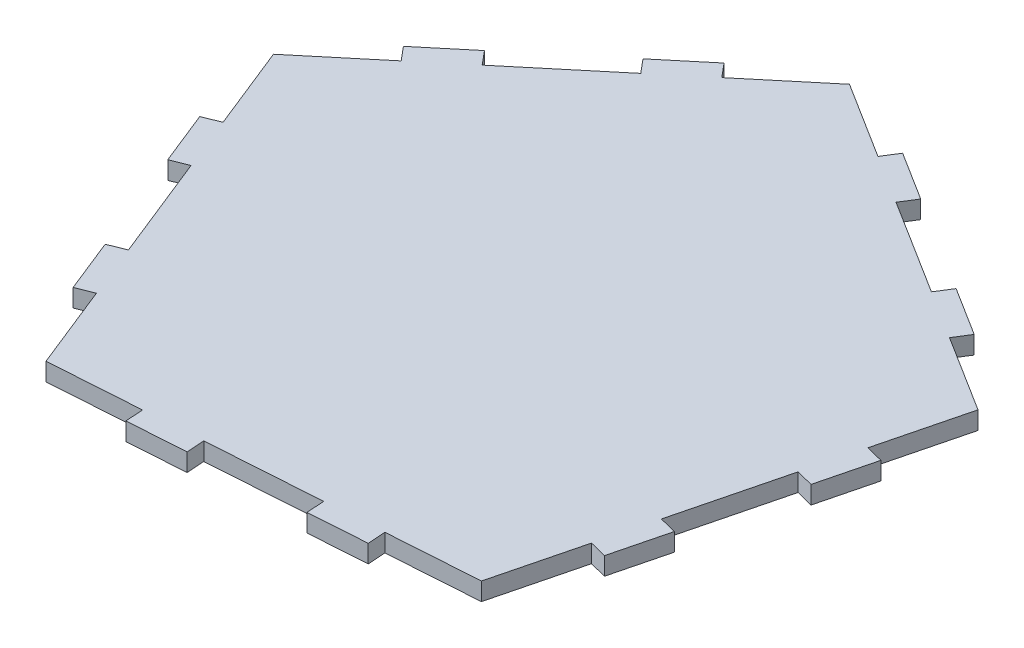
SolidWorks part; units mm, degrees
ref_plane "Front Plane" through (0, 0, 0) normal (0, 0, 1) x (1, 0, 0)
ref_plane "Top Plane" through (0, 0, 0) normal (0, 1, 0) x (1, 0, 0)
ref_plane "Right Plane" through (0, 0, 0) normal (1, 0, 0) x (0, 0, -1)
sketch "Sketch1" plane through (0, 0, 0) normal (0, 1, 0) x (1, 0, 0)
  line L1 (-63.7371, 16.0796) -> (-34.9884, -55.6487)
  line L2 (-34.9884, -55.6487) -> (42.1131, -50.4724)
  line L3 (42.1131, -50.4724) -> (61.0157, 24.4551)
  line L4 (61.0157, 24.4551) -> (-4.4033, 65.5865)
  line L5 (-4.4033, 65.5865) -> (-63.7371, 16.0796)
  circle A0 centre (0, 0) radius 53.18 construction
  dimension "D1" = 106.36
extrude "Boss-Extrude1" add sketch "Sketch1" along normal blind 3.18
sketch "Sketch2" plane through (0, 0, 0) normal (0, -1, 0) x (1, 0, 0)
  line L0 (-56.8852, 1.016) -> (-53.9335, -0.1671)
  line L1 (-56.8852, 1.016) -> (-53.0831, 10.5024)
  line L2 (-53.9335, -0.1671) -> (-50.1313, 9.3193)
  line L3 (-53.0831, 10.5024) -> (-50.1313, 9.3193)
  line L4 (-63.7371, -16.0796) -> (-34.9884, 55.6487) construction
  line L5 (-45.6425, 29.0668) -> (-41.8403, 38.5532)
  line L6 (-45.6425, 29.0668) -> (-42.6907, 27.8837)
  line L7 (-41.8403, 38.5532) -> (-38.8886, 37.3701)
  line L8 (-42.6907, 27.8837) -> (-38.8886, 37.3701)
  line L9 (-49.3628, 19.7846) -> (-19.2439, 7.7129) construction
  dimension "D1" = 3.18
  dimension "D2" = 10.22
  dimension "D3" = 10
extrude "Cut-Extrude1" [suppressed] cut sketch "Sketch2" against normal through all
ref_axis "Axis1" through (0, 3.339, 0) along (0, -1, 0)
pattern_circular "CirPattern1" [suppressed] count 5 over 360 about axis through (0, 3.339, 0) along (0, -1, 0) of bodies 102
sketch "Sketch3" plane through (0, 0, 0) normal (0, -1, 0) x (1, 0, 0)
  line L0 (-56.8852, 1.016) -> (-53.9335, -0.1671)
  line L1 (-56.8852, 1.016) -> (-53.0831, 10.5024)
  line L2 (-53.9335, -0.1671) -> (-50.1313, 9.3193)
  line L3 (-53.0831, 10.5024) -> (-50.1313, 9.3193)
  line L4 (-63.7371, -16.0796) -> (-34.9884, 55.6487) construction
  line L5 (-45.6425, 29.0668) -> (-42.6907, 27.8837)
  line L6 (-45.6425, 29.0668) -> (-41.8403, 38.5532)
  line L7 (-42.6907, 27.8837) -> (-38.8886, 37.3701)
  line L8 (-41.8403, 38.5532) -> (-38.8886, 37.3701)
  line L9 (0, 0) -> (-49.3628, 19.7846) construction
  line L10 (-65.563, -20.6353) -> (-62.6113, -21.8183)
  line L11 (-65.563, -20.6353) -> (-33.4497, 59.4878)
  line L12 (-62.6113, -21.8183) -> (-30.498, 58.3048)
  line L13 (-33.4497, 59.4878) -> (-30.498, 58.3048)
  line M14 (-63.7371, -16.0796) -> (-4.4033, -65.5865)
  line M17 (42.1131, 50.4724) -> (-34.9884, 55.6487)
  line M18 (-34.9884, 55.6487) -> (-63.7371, -16.0796)
  dimension "D1" = 10.22
  dimension "D2" = 10
  dimension "D3" = 3.18
  dimension "D4" = 3.18
extrude "Cut-Extrude2" cut sketch "Sketch3" against normal blind 10 contours L12 L0 M14 M18 | L12 L9 L11 L3 | L9 L12 L5 M18 | L8 L12 M17 M18 region at (-58.9188, 0, -8.3707) region at (-49.747, 0, 14.5519) region at (-46.0267, 0, 23.8342) region at (-36.8281, 0, 46.746)
pattern_circular "CirPattern2" count 5 over 360 about axis through (0, 3.339, 0) along (0, -1, 0) of "Cut-Extrude2"
equation "\"kerf\"= .22mm"
equation "\"tabWidth\"= 10 + \"kerf\" "
equation "\"tabSeperation\" = 10  "
equation "\"tabThickness\"= 3.18"
equation "\"D2@Sketch2\"=\"tabWidth\""
equation "\"D1@Sketch2\"=\"tabThickness\""
equation "\"D3@Sketch2\"=\"tabSeperation\""
equation "\"D2@Sketch3\"=\"tabSeperation\""
equation "\"D3@Sketch3\"=\"tabThickness\""
equation "\"D4@Sketch3\"=\"tabThickness\""
equation "\"tabLength\" = \"kerf\" + 12"
